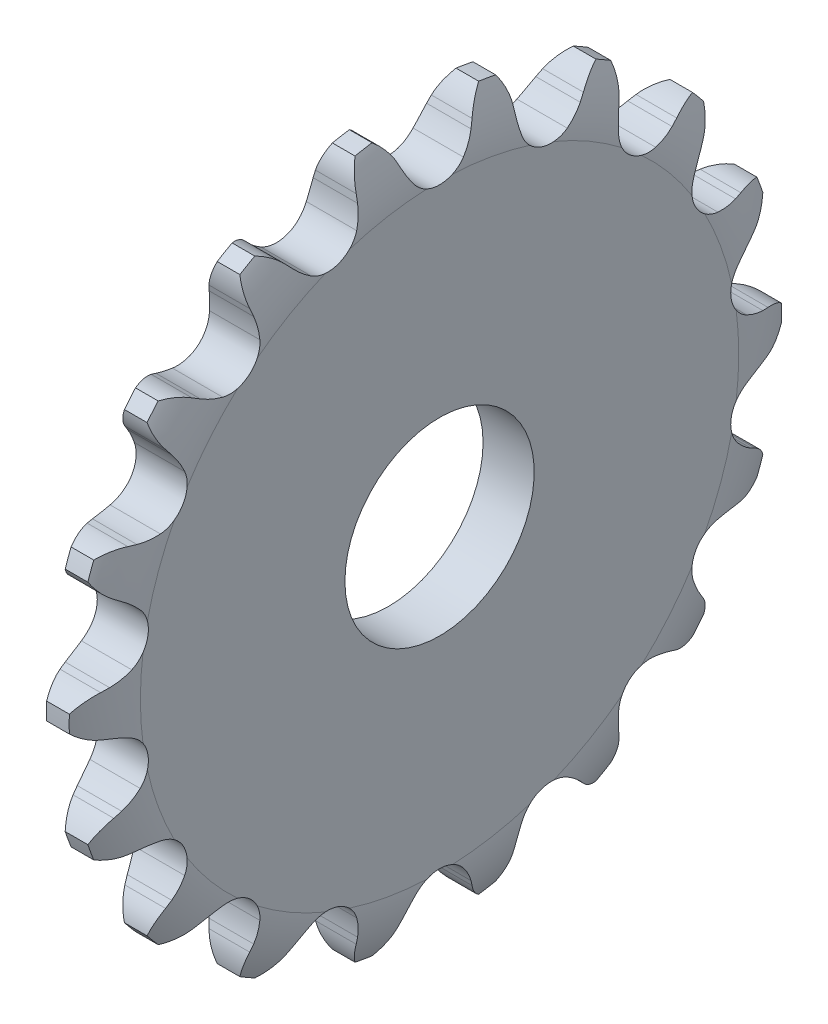
SolidWorks part; units mm, degrees
ref_plane "Plane1" through (0, 0, 0) normal (0, 0, 1) x (1, 0, 0)
ref_plane "Plane2" through (0, 0, 0) normal (0, 1, 0) x (1, 0, 0)
ref_plane "Plane3" through (0, 0, 0) normal (1, 0, 0) x (0, 0, -1)
other "Configuration Table"
sketch "Clipboard" plane through (0, 0, 0) normal (0, 1, 0) x (1, 0, 0)
  line L0 (0, 0) -> (9.0588, -2.9434)
  line L1 (-15, 0) -> (100, 0) construction
  line L2 (0, 0) -> (-0.7911, 0.8941)
  line L3 (0, 0) -> (-4.4605, 1.7048)
  line L4 (0, 0) -> (4.5415, 1.4756)
  line L5 (0, 0) -> (-47.5972, -17.7524)
  line L6 (0, 0) -> (-3.555, -2.3986)
  line L7 (-0.7911, 0.8941) -> (47.2413, 17.433)
  line L8 (-76.2, 38.1) -> (-58.1914, 38.1)
  line L9 (-73.2057, 38.5609) -> (-73.0533, 38.5634)
  line L10 (-73.0533, 76.1892) -> (-62.9187, 76.1892)
  circle A0 centre (0, 0) radius 2.54
  circle A1 centre (0, 0) radius 21.866
  circle A2 centre (0, 0) radius 38.1
  dimension "Num_teeth" = 18
  dimension "Thickness" = 4.2885
sketch "BasProSke" plane through (0, 0, 0) normal (0, 1, 0) x (1, 0, 0)
  line L0 (-10, 0) -> (60, 0) construction
  line L1 (0, 0) -> (0, 25.0918)
  line L2 (0, 0) -> (4.2885, 0)
  line L3 (4.2885, 0) -> (4.2885, 25.0918)
  line L4 (3.0947, 29.867) -> (1.1938, 29.867)
  arc A0 (0, 25.0918) -> (1.1938, 29.867) centre (10.1473, 25.0918) cw
  arc A1 (4.2885, 25.0918) -> (3.0947, 29.867) centre (-5.8588, 25.0918) ccw
  dimension "D1" = 10.1473
  dimension "Thickness" = 4.2885
  dimension "Diameter" = 59.734
  dimension "H1" = 4.7752
  dimension "G1" = 1.1938
revolve "Base-Revolve" add sketch "BasProSke" angle 360 about L0
sketch "GrvSke" plane through (0, 0, 0) normal (0, 1, 0) x (1, 0, 0)
  line L0 (4.2885, 25.0918) -> (4.2885, 21.866)
  line L1 (4.2885, 21.866) -> (10.1346, 21.866)
  line L2 (10.1346, 21.866) -> (10.1346, 25.0918)
  line L3 (3.0947, 29.867) -> (11.3284, 29.867)
  line L4 (7.2116, 0) -> (7.2116, 52.07) construction
  line L5 (-10, 0) -> (60, 0) construction
  line L6 (0, 0) -> (35.56, 0) construction
  arc A0 (10.1346, 25.0918) -> (11.3284, 29.867) centre (20.2819, 25.0918) cw
  arc A1 (4.2885, 25.0918) -> (3.0947, 29.867) centre (-5.8588, 25.0918) ccw
  dimension "Diameter" = 59.734
  dimension "H1" = 4.7752
  dimension "G1" = 1.1938
revolve "Groove" [suppressed] cut sketch "GrvSke" angle 360 about L6
pattern_linear "Grooves" [suppressed]
sketch "TooCutSke" plane through (0, 0, 0) normal (1, 0, 0) x (0, 0, -1)
  line L0 (2.9176, 27.2991) -> (3.16, 27.8581)
  line L1 (0, 0) -> (0, 107) construction
  line L2 (0, 27.4261) -> (-10, 27.4261) construction
  line L3 (-2.9176, 27.2991) -> (-3.16, 27.8581)
  arc A0 (2.0323, 25.8192) -> (2.9176, 27.2991) centre (-3.1879, 29.9468) ccw
  arc A1 (2.0323, 25.8192) -> (-2.0323, 25.8192) centre (0, 27.4261) cw
  arc A2 (3.16, 27.8581) -> (7.004, 30.381) centre (7.004, 26.1912) cw
  arc A3 (-2.0323, 25.8192) -> (-2.9176, 27.2991) centre (3.1879, 29.9468) cw
  arc A4 (-3.16, 27.8581) -> (-7.004, 30.381) centre (-7.004, 26.1912) ccw
  arc A5 (7.004, 30.381) -> (-7.004, 30.381) centre (0, 0) ccw
  dimension "Pitch_radius" = 27.4261
  dimension "V" = 1.235
extrude "ToothCut" cut sketch "TooCutSke" along normal through all
pattern_circular "TeethCuts" count 18 every 20 about axis through (-10, 0, 0) along (1, 0, 0) of "ToothCut"
sketch "HubNeaOneSke" plane through (0, 0, 0) normal (-1, 0, 0) x (0, 0, 1)
  circle A0 centre (0, 0) radius 21.866
  dimension "Diameter" = 43.732
extrude "HubNearOne" [suppressed] add sketch "HubNeaOneSke" along normal blind 46.5115
sketch "HubNeaBotSke" plane through (0, 0, 0) normal (-1, 0, 0) x (0, 0, 1)
  circle A0 centre (0, 0) radius 21.866
  dimension "Diameter" = 43.732
extrude "HubNearBoth" [suppressed] add sketch "HubNeaBotSke" along normal blind 23.2558
ref_plane "FarPln" through (4.2885, 0, 0) normal (1, 0, 0) x (0, 0, -1)
sketch "HubFarSke" plane through (4.2885, 0, 0) normal (1, 0, 0) x (0, 0, -1)
  circle A0 centre (0, 0) radius 21.866
  dimension "Diameter" = 43.732
extrude "HubFar" [suppressed] add sketch "HubFarSke" along normal blind 23.2558
sketch "BorSke" plane through (0, 0, 0) normal (1, 0, 0) x (0, 0, -1)
  circle A0 centre (0, 0) radius 7.9375
  dimension "Diameter" = 15.875
extrude "Bore" cut sketch "BorSke" along normal mid plane 101.6001
sketch "KeySke" plane through (0, 0, 0) normal (1, 0, 0) x (0, 0, -1)
  line L0 (-2.3813, 0) -> (-2.3813, 10.0711)
  line L1 (-2.3813, 10.0711) -> (2.3813, 10.0711)
  line L2 (2.3813, 10.0711) -> (2.3813, 0)
  line L3 (0, 0) -> (0, 34) construction
  line L4 (-2.3813, 0) -> (2.3813, 0)
  dimension "Offset" = 10.0711
  dimension "Width" = 4.7625
extrude "Keyway" [suppressed] cut sketch "KeySke" along normal mid plane 101.6001
pattern_circular "Keyway2" [suppressed] count 2 every 90 about axis through (-10, 0, 0) along (1, 0, 0) reverse direction yes
sketch "Sketch1" plane through (4.2885, 0, 0) normal (1, 0, 0) x (0, 0, -1)
  circle A0 centre (0, 0) radius 9.4843
equation "\"Num_teeth@Clipboard\" = int( \"Num_teeth@Clipboard\" )"
equation "\"Num_teeth@Clipboard\" = ((sgn( \"Num_teeth@Clipboard\" - 5.0)+1)*( \"Num_teeth@Clipboard\" - 5.0))/2 +5.0"
equation "\"Num_teeth@Clipboard\" = ((sgn( \"Num_teeth@Clipboard\" - 200.0)-1)*( \"Num_teeth@Clipboard\" - 200.0))/-2 +200.0"
equation "\"MHD@Clipboard\" = \"Pitch@Clipboard\" * (1.0 / tan(3.14159265 / \"Num_teeth@Clipboard\" ) - 1.0) - 0.03"
equation "\"Thickness@Clipboard\"  = \"Width@Clipboard\" * \"Width_factor@Clipboard\" - \"Width_const@Clipboard\" + (\"Num_strands@Clipboard\" - 1) * \"Transv_pitch@Clipboard\""
equation "\"OAL@Clipboard\" = \"Thickness@Clipboard\""
equation "\"MHD@Clipboard\" = ((sgn( \"MHD@Clipboard\" - \"Hub_dia@Clipboard\" )-1)*( \"MHD@Clipboard\" - \"Hub_dia@Clipboard\" ))/-2+ \"Hub_dia@Clipboard\""
equation "\"OAL@Clipboard\" = ((sgn( \"OAL@Clipboard\" - \"Overall_len@Clipboard\" )+1)*( \"OAL@Clipboard\" - \"Overall_len@Clipboard\" ))/2 + \"Overall_len@Clipboard\" + 0.000002"
equation "\"Num_teeth@TeethCuts\" = int( \"Show_teeth@Clipboard\" ) + 1"
equation "\"Num_teeth@TeethCuts\" = ((sgn( \"Num_teeth@TeethCuts\" - \"Num_teeth@Clipboard\" )-1)*( \"Num_teeth@TeethCuts\" - \"Num_teeth@Clipboard\" ))/-2+ \"Num_teeth@Clipboard\""
equation "\"Num_teeth@TeethCuts\" = ((sgn( \"Num_teeth@TeethCuts\" - 2.0)+1)*( \"Num_teeth@TeethCuts\" - 2.0))/2 +2.0"
equation "\"Angle@TeethCuts\" = 360.0 / \"Num_teeth@Clipboard\""
equation "\"Pitch_radius@TooCutSke\" = ( \"Pitch@Clipboard\" / 2.0) / sin(3.14159265 / \"Num_teeth@Clipboard\" )  'ma"
equation "\"R@TooCutSke\"  = \"Dr@Clipboard\" * 0.5025 + 0.0015"
equation "\"A@TooCutSke\" = 35.0 + (60.0 / \"Num_teeth@Clipboard\")"
equation "\"E@TooCutSke\"  = \"Dr@Clipboard\" * 1.3025 + 0.0015"
equation "\"B@TooCutSke\"  = 18.0 - (56.0 / \"Num_teeth@Clipboard\" )"
equation "\"W@TooCutSke\" = 1.4 * \"Dr@Clipboard\" * cos(3.14159265 / \"Num_teeth@Clipboard\" )"
equation "\"V@TooCutSke\" = 1.4 * \"Dr@Clipboard\" * sin(3.14159265 / \"Num_teeth@Clipboard\" )"
equation "\"Diameter@BasProSke\" = 2.0 * ( (0.3 * \"Pitch@Clipboard\" ) +  \"Pitch@Clipboard\" / 2.0 / tan(3.14159265 / \"Num_teeth@Clipboard\" ))"
equation "\"Thickness@BasProSke\"  = \"Thickness@Clipboard\""
equation "\"G1@BasProSke\" =  \"Chamfer_wid@Clipboard\""
equation "\"G2@BasProSke\" =  \"Chamfer_wid@Clipboard\""
equation "\"H1@BasProSke\" =  \"Chamfer_dep@Clipboard\""
equation "\"H2@BasProSke\" =  \"Chamfer_dep@Clipboard\""
equation "\"Diameter@GrvSke\" = \"Diameter@BasProSke\""
equation "\"G1@GrvSke\" = \"Chamfer_wid@Clipboard\""
equation "\"H1@GrvSke\" = \"Chamfer_dep@Clipboard\""
equation "\"Grv_diam@GrvSke\" =  \"Pitch@Clipboard\" * (1.0 / tan(3.14159265 / \"Num_teeth@Clipboard\" ) - 1.0) - 0.03"
equation "\"Grv_width@GrvSke\" =  \"Transv_pitch@Clipboard\" - ( \"Width@Clipboard\" * \"Width_factor@Clipboard\" - \"Width_const@Clipboard\" )"
equation "\"Offset@GrvSke\" = \"Grv_width@GrvSke\" / 2.0 + ( \"Width@Clipboard\" * \"Width_factor@Clipboard\" - \"Width_const@Clipboard\" )"
equation "\"Offset@Grooves\" = \"Transv_pitch@Clipboard\""
equation "\"Num_grvs@Grooves\" = \"Num_strands@Clipboard\""
equation "\"Num_grvs@Grooves\" = \"Num_grvs@Grooves\" - 1 * sgn( \"Num_grvs@Grooves\" -1)"
equation "\"Diameter@HubNeaOneSke\" = \"MHD@Clipboard\""
equation "\"Length@HubNearOne\" = \"OAL@Clipboard\" - \"Thickness@BasProSke\""
equation "\"Diameter@HubNeaBotSke\" = \"MHD@Clipboard\""
equation "\"Length@HubNearBoth\" = ( \"OAL@Clipboard\" - \"Thickness@BasProSke\" ) / 2.0"
equation "\"Thickness@FarPln\" = \"Thickness@BasProSke\""
equation "\"Diameter@HubFarSke\" = \"MHD@Clipboard\""
equation "\"Length@HubFar\" = ( \"OAL@Clipboard\" - \"Thickness@BasProSke\" ) / 2.0"
equation "\"D1@Bore\" = \"OAL@Clipboard\" * 2.0"
equation "\"D1@Keyway\" = \"OAL@Clipboard\" * 2.0"
equation "\"Offset@KeySke\" = \"T_dim@Clipboard\" - \"Diameter@BorSke\" / 2.0"
